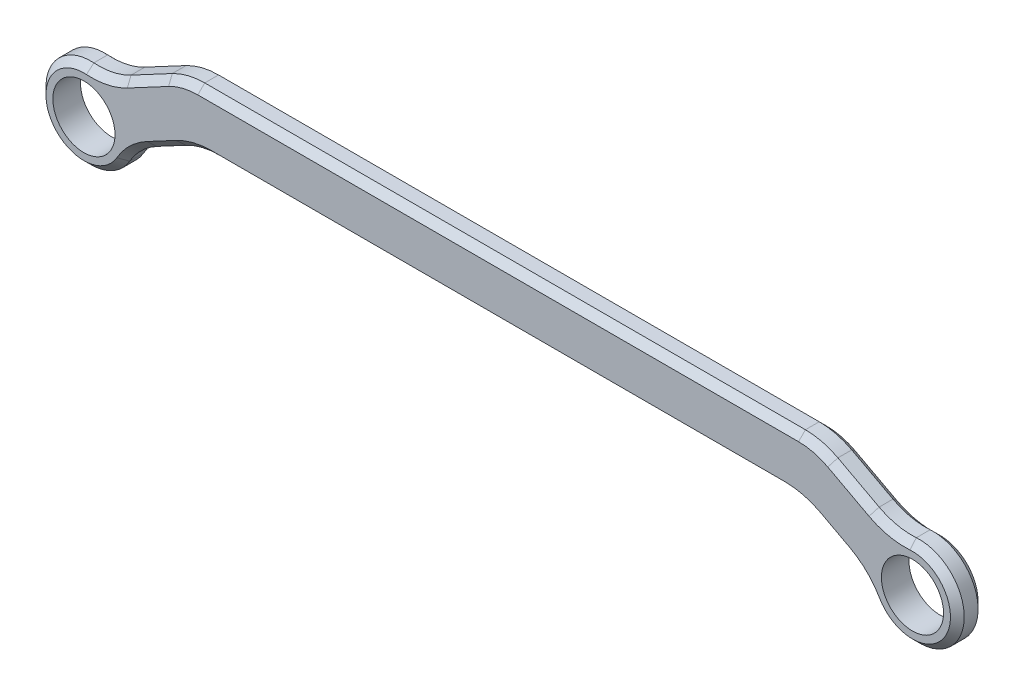
SolidWorks part; units mm, degrees
ref_plane "Front Plane" through (0, 0, 0) normal (0, 0, 1) x (1, 0, 0)
ref_plane "Top Plane" through (0, 0, 0) normal (0, 1, 0) x (1, 0, 0)
ref_plane "Right Plane" through (0, 0, 0) normal (1, 0, 0) x (0, 0, -1)
sketch "Sketch1" plane through (0, 0, 0) normal (0, 0, 1) x (1, 0, 0)
  line L0 (0, 0) -> (120, 0) construction
  line L1 (0, 0) -> (15, 8) construction
  line L3 (15, 8) -> (105, 8) construction
  line L5 (105, 8) -> (120, 0) construction
  line L6 (6.4031, -1.1184) -> (16, 4)
  line L7 (16, 4) -> (104, 4)
  line L8 (104, 4) -> (113.5969, -1.1184)
  line L9 (2.6384, 5.9405) -> (14, 12)
  line L10 (14, 12) -> (106, 12)
  line L11 (106, 12) -> (117.3616, 5.9405)
  line L12 (-1.8824, 3.5294) -> (14, 12) construction
  line L13 (1.8824, -3.5294) -> (16, 4) construction
  line L15 (106, 12) -> (121.8824, 3.5294) construction
  line L17 (104, 4) -> (118.1176, -3.5294) construction
  circle A0 centre (0, 0) radius 4.5
  circle A1 centre (0, 0) radius 6.5
  circle A2 centre (120, 0) radius 4.5
  circle A3 centre (120, 0) radius 6.5
  dimension "D1" = 9
  dimension "D2" = 13
  dimension "D4" = 9
  dimension "D5" = 13
  dimension "D3" = 120
  dimension "D6" = 8
  dimension "D7" = 90
  dimension "D8" = 4
  dimension "D9" = 4
extrude "Boss-Extrude1" add sketch "Sketch1" along normal blind 4 contours A3 L11 L10 L9 A1 L6 L7 L8 | A1 A0 | A3 A2 region at (60, 7.5424, 0) region at (-5.5731, -2.9723, 0) region at (114.4269, 2.9723, 0)
fillet "Fillet1" radius 10 8 edges at (113.5969, -1.1184, 2) (117.3616, 5.9405, 2) (104, 4, 2) (106, 12, 2) (16, 4, 2) (14, 12, 2) (6.4031, -1.1184, 2) (2.6384, 5.9405, 2)
chamfer "Chamfer1" distance 1 angle 45 32 edges at (60, 4, 0) (16.0746, 3.7014, 0) (103.9254, 3.7014, 0) (11.6906, 1.7017, 0) (108.3094, 1.7017, 0) (7.3403, -1.0562, 0) (112.6597, -1.0562, 0) (-5.7353, -3.0588, 0) (125.7353, -3.0588, 0) (3.2121, 6.6842, 0) (116.7879, 6.6842, 0) (8.8083, 9.2311, 0) (111.1917, 9.2311, 0) (14.0746, 11.7014, 0) (105.9254, 11.7014, 0) (60, 12, 0) (60, 4, 4) (16.0746, 3.7014, 4) (103.9254, 3.7014, 4) (11.6906, 1.7017, 4) (108.3094, 1.7017, 4) (7.3403, -1.0562, 4) (112.6597, -1.0562, 4) (-5.7353, -3.0588, 4) (125.7353, -3.0588, 4) (3.2121, 6.6842, 4) (116.7879, 6.6842, 4) (8.8083, 9.2311, 4) (111.1917, 9.2311, 4) (14.0746, 11.7014, 4) (105.9254, 11.7014, 4) (60, 12, 4)
